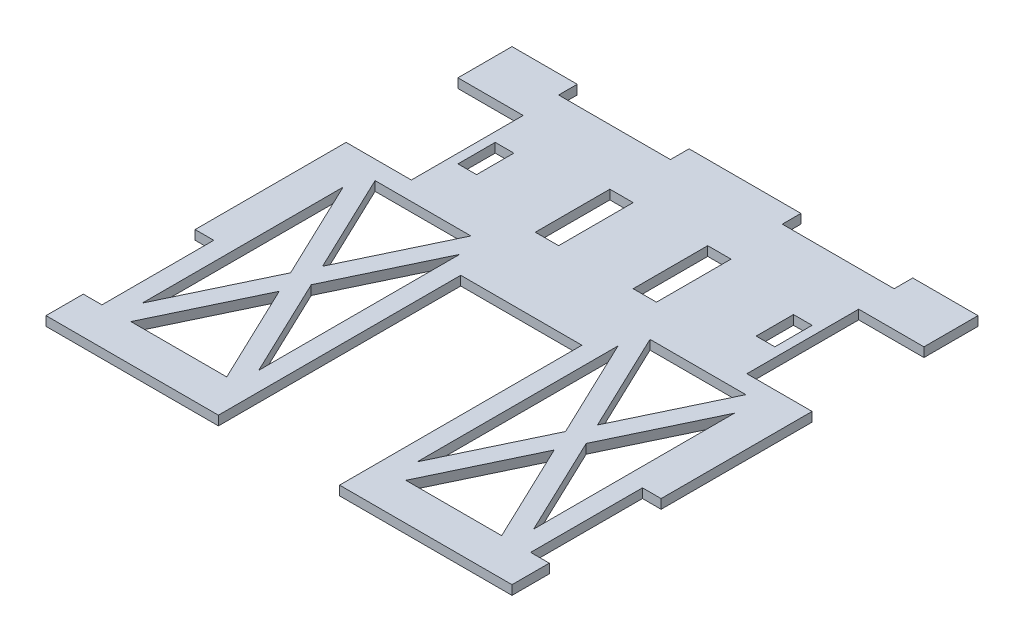
SolidWorks part; units mm, degrees
material "7050-T73510"
ref_plane "Front Plane" through (0, 0, 0) normal (0, 0, 1) x (1, 0, 0)
ref_plane "Top Plane" through (0, 0, 0) normal (0, 1, 0) x (1, 0, 0)
ref_plane "Right Plane" through (0, 0, 0) normal (1, 0, 0) x (0, 0, -1)
sketch "Sketch1" plane through (0, 0, 0) normal (0, 1, 0) x (1, 0, 0)
  line L0 (0, -55) -> (0, 55) construction
  line L1 (-158.75, -76.2) -> (158.75, -76.2)
  line L2 (-158.75, -76.2) -> (-158.75, 76.2)
  line L3 (-158.75, 76.2) -> (158.75, 76.2)
  line L4 (158.75, -76.2) -> (158.75, 76.2)
  line L5 (-158.75, -76.2) -> (158.75, 76.2) construction
  line L6 (-158.75, 76.2) -> (158.75, -76.2) construction
  line L7 (-158.75, -76.2) -> (-25.4, -76.2)
  line L8 (-158.75, -76.2) -> (-158.75, -241.3)
  line L9 (-158.75, -241.3) -> (-25.4, -241.3)
  line L10 (-25.4, -76.2) -> (-25.4, -241.3)
  line L11 (25.4, -76.2) -> (25.4, -241.3)
  line L12 (158.75, -241.3) -> (25.4, -241.3)
  line L13 (158.75, -76.2) -> (158.75, -241.3)
  line L14 (158.75, -76.2) -> (25.4, -76.2)
  line L15 (-41.275, -76.2) -> (-41.275, -241.3)
  line L16 (41.275, -76.2) -> (41.275, -241.3)
  point P0 (0, 0)
  dimension "D1" = 317.5
  dimension "D2" = 152.4
  dimension "D3" = 317.5
  dimension "D4" = 50.8
  dimension "D5" = 15.875
extrude "Boss-Extrude1" add sketch "Sketch1" along normal blind 6.35 contours L15 L1 L8 L9 | L14 L16 L12 L13 | L1 L7 L14 L4 L3 L2 region at (0, 0, 0) region at (-100.0125, 0, 158.75) region at (100.0125, 0, 158.75)
sketch "Sketch2" plane through (0, 6.35, 0) normal (0, 1, 0) x (1, 0, 0)
  line L0 (158.75, -241.3) -> (158.75, 76.2) construction
  line L1 (158.75, 39.37) -> (114.3, 39.37)
  line L2 (158.75, 39.37) -> (158.75, -36.83)
  line L3 (158.75, -36.83) -> (114.3, -36.83)
  line L4 (114.3, 39.37) -> (114.3, -36.83)
  line L5 (-158.75, 76.2) -> (158.75, 76.2) construction
  line L6 (158.75, -139.7) -> (146.05, -139.7)
  line L7 (158.75, -139.7) -> (158.75, -215.9)
  line L8 (158.75, -215.9) -> (146.05, -215.9)
  line L9 (146.05, -139.7) -> (146.05, -215.9)
  line L10 (0, -3.4925) -> (0, 3.4925) construction
  line L11 (-158.75, -215.9) -> (-146.05, -215.9)
  line L12 (-146.05, -139.7) -> (-146.05, -215.9)
  line L13 (-158.75, -139.7) -> (-146.05, -139.7)
  line L14 (-158.75, -139.7) -> (-158.75, -215.9)
  line L15 (-158.75, -36.83) -> (-114.3, -36.83)
  line L16 (-114.3, 39.37) -> (-114.3, -36.83)
  line L17 (-158.75, 39.37) -> (-114.3, 39.37)
  line L18 (-158.75, 39.37) -> (-158.75, -36.83)
  line L19 (-114.3, 63.5) -> (-38.1, 63.5)
  line L20 (114.3, 76.2) -> (38.1, 76.2)
  line L21 (114.3, 76.2) -> (114.3, 63.5)
  line L22 (114.3, 63.5) -> (38.1, 63.5)
  line L23 (38.1, 76.2) -> (38.1, 63.5)
  line L24 (-38.1, 76.2) -> (-38.1, 63.5)
  line L25 (-114.3, 76.2) -> (-38.1, 76.2)
  line L26 (-114.3, 76.2) -> (-114.3, 63.5)
  point P30 (0, 0)
  point P31 (0, 0)
  dimension "D1" = 44.45
  dimension "D2" = 12.7
  dimension "D3" = 76.2
  dimension "D4" = 76.2
  dimension "D5" = 36.83
  dimension "D6" = 215.9
  dimension "D7" = 76.2
  dimension "D8" = 12.7
  dimension "D9" = 76.2
extrude "Cut-Extrude1" cut sketch "Sketch2" against normal through all
sketch "Sketch4" plane through (0, 6.35, 0) normal (0, 1, 0) x (1, 0, 0)
  line L0 (41.275, -76.2) -> (41.275, -241.3) construction
  line L1 (53.975, -215.9) -> (133.35, -215.9)
  line L2 (53.975, -215.9) -> (53.975, -49.53)
  line L3 (53.975, -49.53) -> (133.35, -49.53)
  line L4 (133.35, -215.9) -> (133.35, -49.53)
  line L5 (146.05, -139.7) -> (146.05, -215.9) construction
  line L6 (158.75, -241.3) -> (41.275, -241.3) construction
  line L7 (53.975, -215.9) -> (133.35, -49.53) construction
  line L8 (53.975, -49.53) -> (133.35, -215.9) construction
  line L9 (133.35, -201.1532) -> (61.0107, -49.53)
  line L10 (126.3143, -215.9) -> (53.975, -64.2768)
  line L11 (53.975, -201.1532) -> (126.3143, -49.53)
  line L12 (61.0107, -215.9) -> (133.35, -64.2768)
  line L13 (114.3, -36.83) -> (158.75, -36.83) construction
  line L14 (0, -3.4925) -> (0, 3.4925) construction
  line L15 (-53.975, -201.1532) -> (-126.3143, -49.53)
  line L16 (-126.3143, -215.9) -> (-53.975, -64.2768)
  line L17 (-133.35, -201.1532) -> (-61.0107, -49.53)
  line L18 (-61.0107, -215.9) -> (-133.35, -64.2768)
  line L19 (-53.975, -49.53) -> (-133.35, -49.53)
  line L20 (-133.35, -215.9) -> (-133.35, -49.53)
  line L21 (-53.975, -215.9) -> (-133.35, -215.9)
  line L22 (-53.975, -215.9) -> (-53.975, -49.53)
  point P18 (116.9135, -166.7022)
  dimension "D1" = 12.7
  dimension "D2" = 12.7
  dimension "D3" = 25.4
  dimension "D4" = 12.7
  dimension "D5" = 12.7
extrude "Cut-Extrude3" cut sketch "Sketch4" against normal through all contours L12 L9 L4 | L12 L1 L10 | L2 L11 L10 | L9 L11 L3 | L21 L18 L16 | L20 L17 L18 | L17 L19 L15 | L15 L22 L16 region at (93.6625, 6.35, 193.0873) region at (64.8589, 6.35, 132.715) region at (122.4661, 6.35, 132.715) region at (93.6625, 6.35, 72.3427) region at (-64.8589, 6.35, 132.715) region at (-93.6625, 6.35, 72.3427) region at (-93.6625, 6.35, 193.0873) region at (-122.4661, 6.35, 132.715)
sketch "Sketch3" plane through (0, 6.35, 0) normal (0, 1, 0) x (1, 0, 0)
  line L0 (-41.275, -76.2) -> (41.275, -76.2) construction
  line L1 (-41.275, -25.4) -> (-25.4, -25.4)
  line L2 (-41.275, -25.4) -> (-41.275, 25.4)
  line L3 (-41.275, 25.4) -> (-25.4, 25.4)
  line L4 (-25.4, -25.4) -> (-25.4, 25.4)
  line L5 (0, -3.4925) -> (0, 3.4925) construction
  line L6 (41.275, 25.4) -> (25.4, 25.4)
  line L7 (25.4, -25.4) -> (25.4, 25.4)
  line L8 (41.275, -25.4) -> (25.4, -25.4)
  line L9 (41.275, -25.4) -> (41.275, 25.4)
  line L10 (114.3, 39.37) -> (114.3, -36.83) construction
  line L11 (95.25, 13.97) -> (107.95, 13.97)
  line L12 (95.25, 13.97) -> (95.25, -11.43)
  line L13 (95.25, -11.43) -> (107.95, -11.43)
  line L14 (107.95, 13.97) -> (107.95, -11.43)
  line L15 (38.1, 63.5) -> (114.3, 63.5) construction
  line L16 (-95.25, -11.43) -> (-107.95, -11.43)
  line L17 (-107.95, 13.97) -> (-107.95, -11.43)
  line L18 (-95.25, 13.97) -> (-107.95, 13.97)
  line L19 (-95.25, 13.97) -> (-95.25, -11.43)
  dimension "D1" = 50.8
  dimension "D2" = 15.875
  dimension "D3" = 50.8
  dimension "D4" = 50.8
  dimension "D5" = 25.4
  dimension "D6" = 12.7
  dimension "D7" = 6.35
  dimension "D8" = 49.53
extrude "Cut-Extrude2" cut sketch "Sketch3" against normal through all
